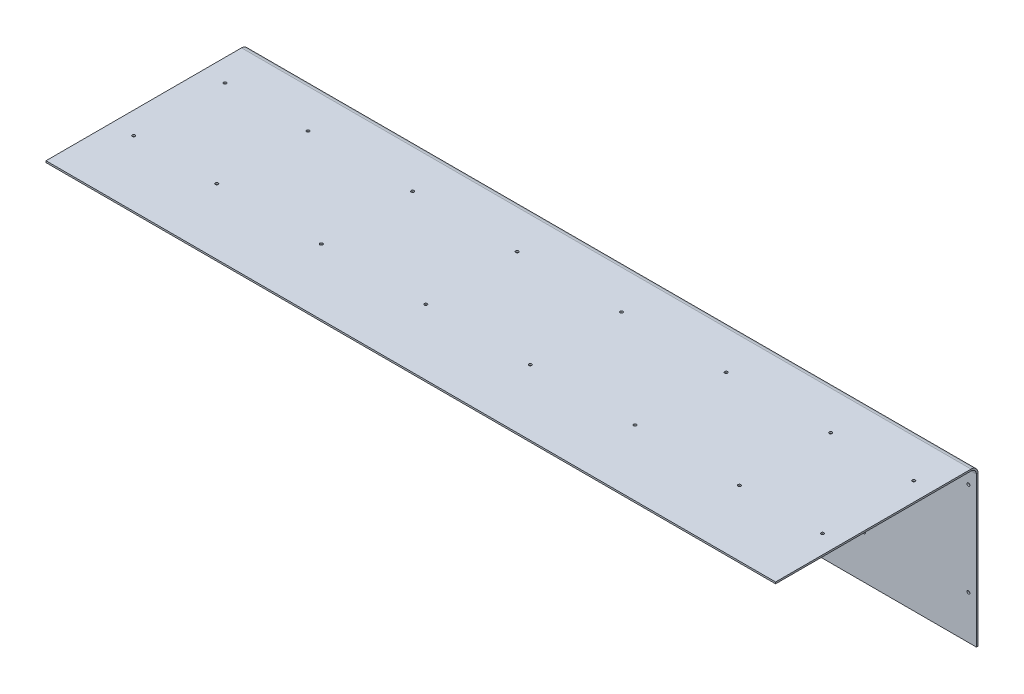
SolidWorks part; units mm, degrees
note: The reader was unsure of these and kept them because the rebuilt part matched: flange length of "Brida de arista1".
material "AISI 1020 Acero laminado en frío"
ref_plane "Alzado" through (0, 0, 0) normal (0, 0, 1) x (1, 0, 0)
ref_plane "Planta" through (0, 0, 0) normal (0, 1, 0) x (1, 0, 0)
ref_plane "Vista lateral" through (0, 0, 0) normal (1, 0, 0) x (0, 0, -1)
sketch "Croquis1" plane through (0, 0, 0) normal (0, 1, 0) x (1, 0, 0)
  line L1 (-709.7806, 428.519) -> (686.2194, 428.519)
  line L2 (-709.7806, 428.519) -> (-709.7806, 41.219)
  line L3 (-709.7806, 41.219) -> (686.2194, 41.219)
  line L4 (686.2194, 428.519) -> (686.2194, 41.219)
  dimension "D1" = 1396
  dimension "D2" = 387.3
base flange "Brida base1" sketch "Croquis1" thickness 3.175 reverse thickness direction no parameters "D1"=10
hole_wizard "Taladro de margen para M51" positions "Croquis3" profile "Croquis2" hole size "M5" standard "Ansi Metric" end condition through all
sketch "Croquis3" plane through (0, -3.175, 0) normal (0, -1, 0) x (-1, 0, 0)
  line L0 (709.7806, 41.219) -> (-686.2194, 41.219) construction
  line L1 (-686.2194, 428.519) -> (709.7806, 428.519) construction
  line L2 (709.7806, 428.519) -> (709.7806, 41.219) construction
  point P0 (508.4306, 166.619)
  point P2 (508.4306, 341.219)
  point P19 (308.4306, 166.619)
  point P20 (308.4306, 341.219)
  point P21 (108.4306, 166.619)
  point P22 (108.4306, 341.219)
  point P23 (-91.5694, 166.619)
  point P24 (-91.5694, 341.219)
  point P25 (-291.5694, 166.619)
  point P26 (-291.5694, 341.219)
  point P27 (-491.5694, 166.619)
  point P28 (-491.5694, 341.219)
  point P34 (667.4306, 166.619)
  point P35 (667.4306, 341.219)
  point P39 (-650.5694, 166.619)
  point P40 (-650.5694, 341.219)
  dimension "D1" = 125.4
  dimension "D2" = 87.3
  dimension "D3" = 201.35
  dimension "D4" = 6
  dimension "D5" = 2
  dimension "D6" = 2
sketch "Croquis2" plane through (-508.4306, -3.175, -166.619) normal (1, 0, 0) x (0, 0, -1)
  line L0 (0, 0) -> (0, 3.175)
  line L1 (0, 3.175) -> (2.75, 3.175)
  line L2 (2.75, 3.175) -> (2.75, 0)
  line L5 (2.75, 0) -> (0, 0)
  line L11 (0, -6.35) -> (0, 107.95) construction
  dimension "Diámetro de taladro hasta el siguiente" = 5.5
  dimension "Profundidad de taladro hasta el siguiente" = 3.175
edge flange "Brida de arista1" sketch "Croquis6" flange angle 90 flange length 300 flange position material inside bend radius 10 thickness 3.175 relief rectangular parameters "D6"=10
sketch "Croquis6" plane through (0, -3.175, -428.519) normal (0, 0, -1) x (1, 0, 0)
  line L0 (686.2194, 0) -> (-709.7806, 0) construction
  line L1 (686.2194, 0) -> (-709.7806, 0)
  line L2 (-709.7806, 0) -> (-709.7806, 296.825)
  line L3 (-709.7806, 296.825) -> (686.2194, 296.825)
  line L4 (686.2194, 296.825) -> (686.2194, 0)
bend "Pliegue de arista1" bend radius 10 bend angle 90 parameters "D5"=1
hole_wizard "Taladro de margen para M52" positions "Croquis8" profile "Croquis7" hole size "M5" standard "Ansi Metric" end condition through all
sketch "Croquis8" plane through (0, 0, -425.344) normal (0, 0, 1) x (1, 0, 0)
  line L1 (-709.7806, -300) -> (-709.7806, -13.175) construction
  line L2 (686.2194, -300) -> (-709.7806, -300) construction
  point P19 (-687.9306, -216.9)
  point P20 (-687.9306, -38.2)
  point P31 (-487.9306, -216.9)
  point P32 (-487.9306, -38.2)
  point P33 (-287.9306, -216.9)
  point P34 (-287.9306, -38.2)
  point P37 (-128.9306, -216.9)
  point P38 (-128.9306, -38.2)
  point P43 (71.0694, -216.9)
  point P44 (71.0694, -38.2)
  point P45 (271.0694, -216.9)
  point P46 (271.0694, -38.2)
  point P47 (471.0694, -216.9)
  point P48 (471.0694, -38.2)
  point P49 (671.0694, -216.9)
  point P50 (671.0694, -38.2)
  dimension "D2" = 21.85
  dimension "D3" = 178.7
  dimension "D4" = 2
  dimension "D5" = 5
  dimension "D6" = 83.1
  dimension "D7" = 159
  dimension "D1" = 3
sketch "Croquis7" plane through (-687.9306, -216.9, -425.344) normal (1, 0, 0) x (0, -1, 0)
  line L0 (0, 0) -> (0, 3.175)
  line L1 (0, 3.175) -> (2.75, 3.175)
  line L2 (2.75, 3.175) -> (2.75, 0)
  line L5 (2.75, 0) -> (0, 0)
  line L11 (0, -6.35) -> (0, 107.95) construction
  dimension "Diámetro de taladro hasta el siguiente" = 5.5
  dimension "Profundidad de taladro hasta el siguiente" = 3.175
sketch "Líneas de pliegue1" [suppressed] plane through (0, 0, 0) normal (0, 1, 0) x (1, 0, 0)
sketch "Cuadro delimitador1" [suppressed] plane through (0, 0, 0) normal (0, 1, 0) x (1, 0, 0)
sheet metal parameters "Chapa metálica1" thickness 3.175 parameters "D1"=10
flat pattern "Chapa desplegada1" [suppressed]
sketch "Líneas de pliegue2" plane through (0, 0, 0) normal (0, 1, 0) x (1, 0, 0)
sketch3d "Cuadro delimitador2" [suppressed]
  line L0 (-686.2194, 28.519, 0) -> (709.7806, 28.519, 0) construction
  line L1 (-686.2194, 428.519, 0) -> (709.7806, 428.519, 0) construction
  line L2 (-686.2194, 28.519, 0) -> (-686.2194, 428.519, 0) construction
  line L3 (709.7806, 28.519, 0) -> (709.7806, 428.519, 0) construction
sheet metal parameters "Chapa metálica2" thickness 3.175 parameters "D1"=10
flat pattern "Chapa desplegada1"
sketch "Líneas de pliegue2" plane through (0, 0, 0) normal (0, 1, 0) x (1, 0, 0)
sketch3d "Cuadro delimitador2" [suppressed]
  line L0 (686.2194, 41.219, 0) -> (-709.7806, 41.219, 0) construction
  line L1 (686.2194, 428.519, 0) -> (-709.7806, 428.519, 0) construction
  line L2 (686.2194, 41.219, 0) -> (686.2194, 428.519, 0) construction
  line L3 (-709.7806, 41.219, 0) -> (-709.7806, 428.519, 0) construction
sheet metal parameters "Chapa metálica3" thickness 3.175 parameters "D1"=10
flat pattern "Chapa desplegada1"
sketch "Líneas de pliegue2" plane through (0, 0, 0) normal (0, 1, 0) x (1, 0, 0)
  line L0 (686.2194, 424.4448) -> (-709.7806, 424.4448) construction
  line L1 (686.2194, 424.4448) -> (-709.7806, 424.4448) construction
sketch3d "Cuadro delimitador2" [suppressed]
  line L0 (686.2194, 41.219, 0) -> (-709.7806, 41.219, 0) construction
  line L1 (686.2194, 720.3706, 0) -> (-709.7806, 720.3706, 0) construction
  line L2 (686.2194, 41.219, 0) -> (686.2194, 720.3706, 0) construction
  line L3 (-709.7806, 41.219, 0) -> (-709.7806, 720.3706, 0) construction
bend of the flat pattern "Aplanar-<Pliegue de arista1>1"
sheet metal parameters "Chapa metálica4" thickness 3.175 parameters "D1"=10
flat pattern "Chapa desplegada1"
sketch "Líneas de pliegue2" plane through (0, 0, 0) normal (0, 1, 0) x (1, 0, 0)
  line L0 (686.2194, 424.4448) -> (-709.7806, 424.4448) construction
  line L1 (686.2194, 424.4448) -> (-709.7806, 424.4448) construction
sketch3d "Cuadro delimitador2" [suppressed]
  line L0 (686.2194, 41.219, 0) -> (-709.7806, 41.219, 0) construction
  line L1 (686.2194, 720.3706, 0) -> (-709.7806, 720.3706, 0) construction
  line L2 (686.2194, 41.219, 0) -> (686.2194, 720.3706, 0) construction
  line L3 (-709.7806, 41.219, 0) -> (-709.7806, 720.3706, 0) construction
bend of the flat pattern "Aplanar-<Pliegue de arista1>1"
